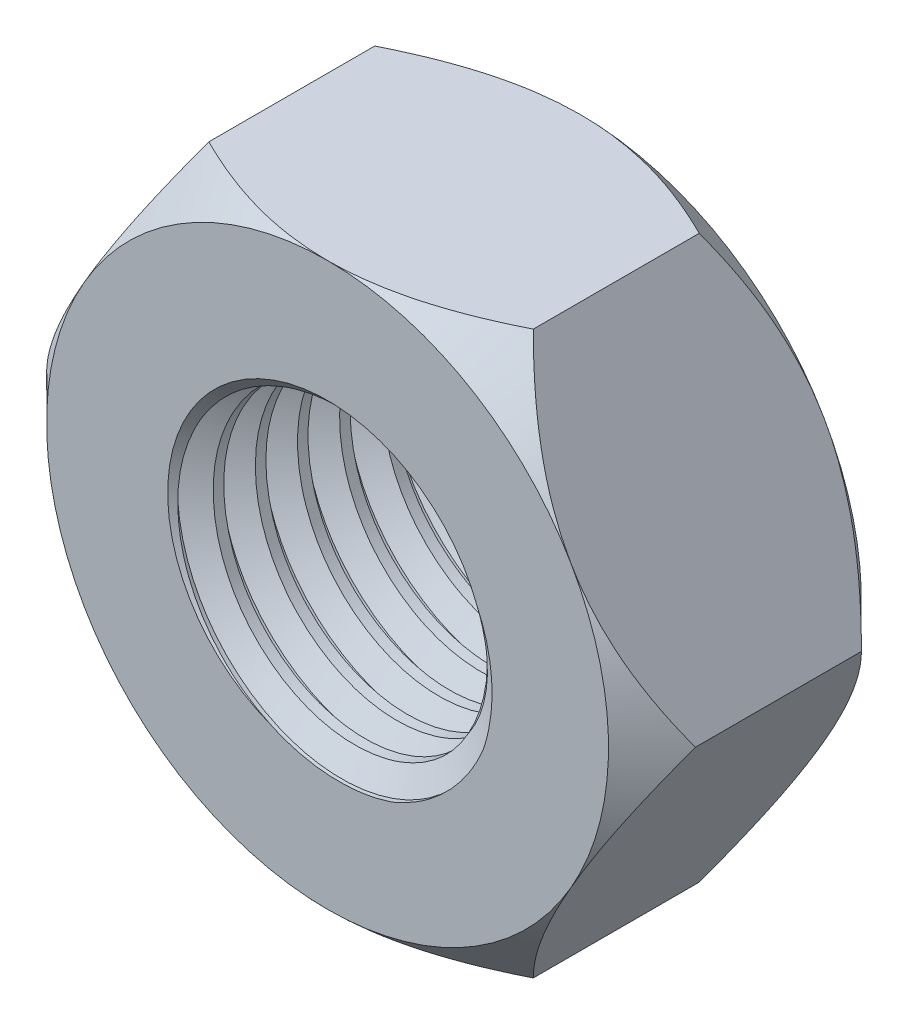
SolidWorks part; units mm, degrees
ref_plane "Front Plane" through (0, 0, 0) normal (0, 0, 1) x (1, 0, 0)
ref_plane "Top Plane" through (0, 0, 0) normal (0, 1, 0) x (1, 0, 0)
ref_plane "Right Plane" through (0, 0, 0) normal (1, 0, 0) x (0, 0, -1)
sketch "Sketch1" plane through (0, 0, 0) normal (0, 0, 1) x (1, 0, 0)
  line L1 (5.7735, -10) -> (11.547, 0)
  line L2 (11.547, 0) -> (5.7735, 10)
  line L3 (5.7735, 10) -> (-5.7735, 10)
  line L4 (-5.7735, 10) -> (-11.547, 0)
  line L5 (-11.547, 0) -> (-5.7735, -10)
  line L6 (-5.7735, -10) -> (5.7735, -10)
  circle A0 centre (0, 0) radius 10 construction
  dimension "D1" = 20
extrude "Boss-Extrude1" add sketch "Sketch1" along normal mid plane 9
sketch "Sketch2" plane through (0, 0, 4.5) normal (0, 0, 1) x (1, 0, 0)
  circle A0 centre (0, 0) radius 10
  point P4 (0, 0)
extrude "Cut-Extrude2" cut sketch "Sketch2" against normal through all draft 45 flip side to cut contours A0
mirror "Mirror1" about plane through (0, 0, 0) normal (0, 0, 1) of "Cut-Extrude2"
sketch "Sketch4" plane through (0, 0, 4.5) normal (0, 0, 1) x (1, 0, 0)
  circle A0 centre (0, 0) radius 5.19
  dimension "D1" = 10.38
extrude "Cut-Extrude3" cut sketch "Sketch4" against normal through all
chamfer "Chamfer1" distance 0.5 angle 45 1 edges at (5.19, 0, 4.5)
thread "Thread1" pitch 1.5 method cut profile "Thread Profile1" start angle 0, offset 2, length 0, pitch 1.5, diameter 10.38
ref_plane "Plane1" through (-5.19, 0, 6) normal (0, -1, 0) x (-1, 0, 0)
sketch "Thread Profile1" plane through (-5.19, 0, 6) normal (0, -1, 0) x (-1, 0, 0)
  line L0 (0, 0) -> (0, 1.5) construction
  line L1 (0, 0) -> (0.8119, 0.4687)
  line L2 (0.8119, 0.4687) -> (0.8119, 0.6562)
  line L3 (0.8119, 0.6562) -> (0, 1.125)
  line L4 (0.8119, 0.5625) -> (0, 0.5625) construction
  line L11 (0, 0) -> (0, 1.125)
  point P2 (0, 0)
  dimension "Pitch" = 1.5
  dimension "Profile_Angle" = 60
  dimension "Profile_Land" = 0.1875
  dimension "Profile_Height" = 0.8119
